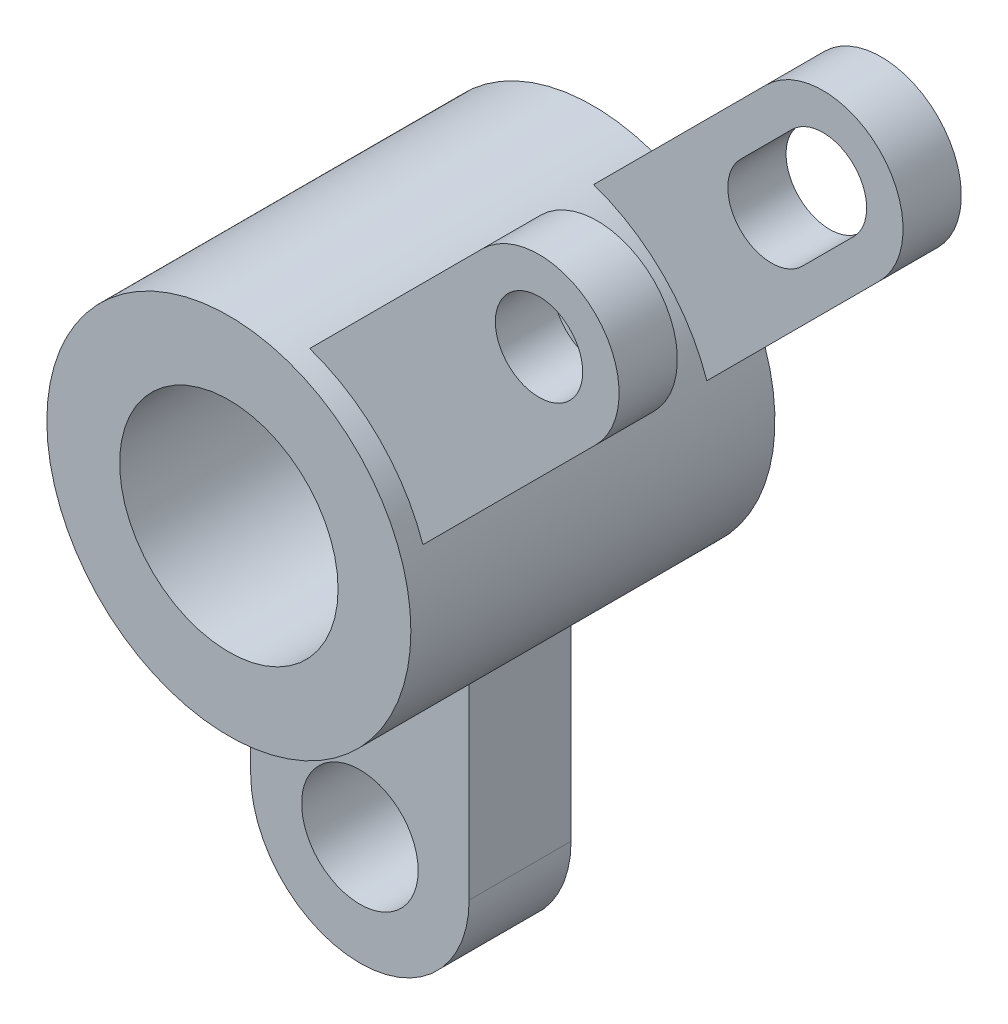
SolidWorks part; units mm, degrees
ref_plane "Спереди" through (0, 0, 0) normal (0, 0, 1) x (1, 0, 0)
ref_plane "Сверху" through (0, 0, 0) normal (0, 1, 0) x (1, 0, 0)
ref_plane "Справа" through (0, 0, 0) normal (1, 0, 0) x (0, 0, -1)
sketch "Эскиз1" plane through (0, 0, 0) normal (0, 0, 1) x (1, 0, 0)
  line L0 (0, 0) -> (19.799, 19.799) construction
  line L1 (-3.8891, 3.8891) -> (15.9099, 23.6881)
  line L2 (3.8891, -3.8891) -> (23.6881, 15.9099)
  line L3 (0, 0) -> (37.813, 0) construction
  circle A0 centre (0, 0) radius 7.5
  circle A1 centre (0, 0) radius 12.5
  arc A2 (-3.8891, 3.8891) -> (3.8891, -3.8891) centre (0, 0) ccw
  arc A3 (23.6881, 15.9099) -> (15.9099, 23.6881) centre (19.799, 19.799) ccw
  circle A4 centre (19.799, 19.799) radius 3
  point P4 (9.8995, 9.8995)
  dimension "D1" = 15
  dimension "D2" = 25
  dimension "D6" = 6
  dimension "D3" = 11
  dimension "D4" = 28
  dimension "D5" = 45
extrude "Бобышка-Вытянуть1" add sketch "Эскиз1" along normal blind 25 contours L1 A1 L2 A0 | L2 A1 L1 A0 region at (-5.5533, -5.5533, 0) region at (6.6396, 6.6396, 0)
extrude "Бобышка-Вытянуть3" add sketch "Эскиз1<4>" along normal blind 4 contours L2 A3 L1 A1 A4 region at (15.1299, 15.1299, 0)
sketch "Эскиз1<4>" plane through (0, 0, 0) normal (0, 0, 1) x (1, 0, 0) same geometry as "Эскиз1"
ref_plane "Плоскость1" through (0, 0, 12.5) normal (0, 0, 1) x (1, 0, 0)
ref_plane "Плоскость2" through (0, 0, 23.5) normal (0, 0, 1) x (1, 0, 0)
sketch "Эскиз2" plane through (0, 0, 23.5) normal (0, 0, 1) x (1, 0, 0)
  line L0 (4.0482, 11.8263) -> (15.9099, 23.6881) construction
  line L1 (11.8263, 4.0482) -> (23.6881, 15.9099) construction
  line L2 (4.0482, 11.8263) -> (15.9099, 23.6881)
  line L3 (11.8263, 4.0482) -> (23.6881, 15.9099)
  arc A0 (23.6881, 15.9099) -> (15.9099, 23.6881) centre (19.799, 19.799) ccw construction
  arc A1 (23.6881, 15.9099) -> (15.9099, 23.6881) centre (19.799, 19.799) ccw
  arc A2 (11.8263, 4.0482) -> (4.0482, 11.8263) centre (0, 0) ccw construction
  arc A3 (11.8263, 4.0482) -> (4.0482, 11.8263) centre (0, 0) ccw
extrude "Бобышка-Вытянуть4" add sketch "Эскиз2" against normal blind 4 contours A1 L2 A3 L3
sketch "Эскиз3" plane through (0, 0, 19.5) normal (0, 0, -1) x (-1, 0, 0)
  circle A0 centre (-19.799, 19.799) radius 3 construction
  circle A1 centre (-19.799, 19.799) radius 3
extrude "Вырез-Вытянуть1" cut sketch "Эскиз3" against normal through all
sketch "Эскиз4" plane through (0, 0, 0) normal (0, 0, -1) x (-1, 0, 0)
  line L0 (-19.799, 19.799) -> (-16.2635, 16.2635) construction
  line L1 (-17.6777, 21.9203) -> (-14.1421, 18.3848)
  line L2 (-21.9203, 17.6777) -> (-18.3848, 14.1421)
  arc A0 (-17.6777, 21.9203) -> (-21.9203, 17.6777) centre (-19.799, 19.799) ccw
  arc A1 (-18.3848, 14.1421) -> (-14.1421, 18.3848) centre (-16.2635, 16.2635) ccw
  circle A2 centre (-19.799, 19.799) radius 3 construction
  point P3 (-18.0312, 18.0312)
  dimension "D1" = 5
extrude "Вырез-Вытянуть2" cut sketch "Эскиз4" against normal up to next
sketch "Эскиз5" plane through (0, 0, 12.5) normal (0, 0, 1) x (1, 0, 0)
  line L0 (7.5, -23) -> (7.5, -10)
  line L1 (-7.5, -23) -> (-7.5, -10)
  line L2 (-7.5, -10) -> (7.5, -10)
  circle A0 centre (0, -23) radius 4
  circle A1 centre (0, -23) radius 7.5
  circle A2 centre (0, 0) radius 12.5 construction
  dimension "D1" = 15
  dimension "D2" = 8
  dimension "D3" = 13
extrude "Бобышка-Вытянуть5" add sketch "Эскиз5" along normal mid plane 7 contours A1 A0 | A1 L0 L2 L1 region at (0, -13.7518, 12.5) region at (0, -30.2879, 12.5)
